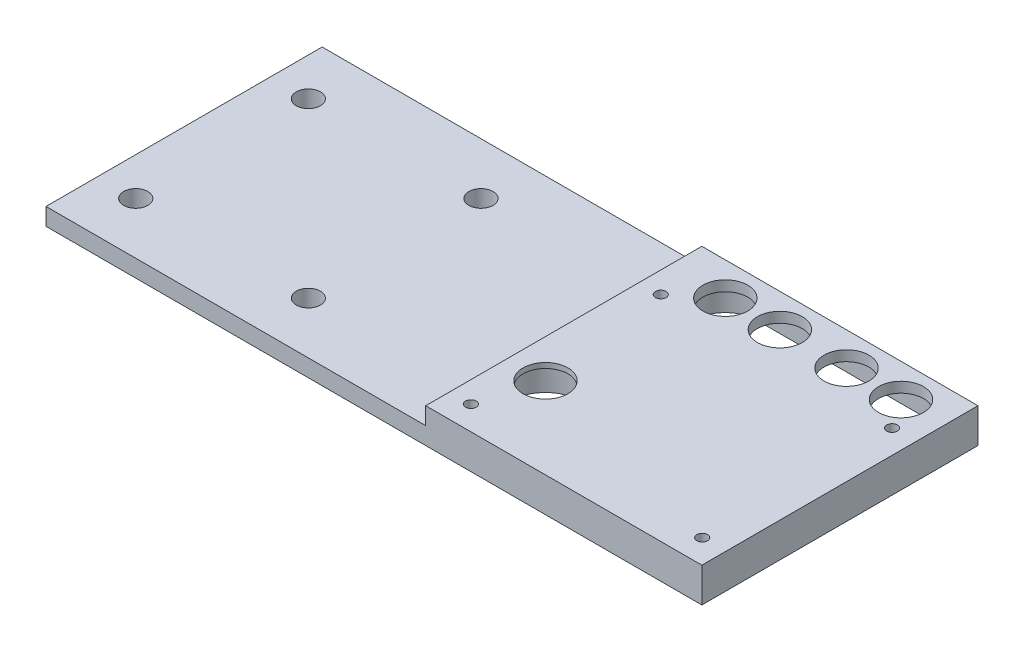
SolidWorks part; units mm, degrees
ref_plane "Front Plane" through (0, 0, 0) normal (0, 0, 1) x (1, 0, 0)
ref_plane "Top Plane" through (0, 0, 0) normal (0, 1, 0) x (1, 0, 0)
ref_plane "Right Plane" through (0, 0, 0) normal (1, 0, 0) x (0, 0, -1)
sketch "Sketch1" plane through (0, 0, 0) normal (0, 1, 0) x (1, 0, 0)
  line L1 (-95, 40) -> (95, 40)
  line L2 (-95, 40) -> (-95, -40)
  line L3 (-95, -40) -> (95, -40)
  line L4 (95, 40) -> (95, -40)
  line L5 (-95, 40) -> (95, -40) construction
  line L6 (-95, -40) -> (95, 40) construction
  point P0 (0, 0)
  dimension "D1" = 80
  dimension "D2" = 190
extrude "Boss-Extrude1" add sketch "Sketch1" along normal blind 5
sketch "Sketch3" plane through (0, 5, 0) normal (0, 1, 0) x (1, 0, 0)
  line L0 (-95, -40) -> (95, -40) construction
  line L1 (95, 40) -> (15, 40)
  line L2 (95, 40) -> (95, -40)
  line L3 (95, -40) -> (15, -40)
  line L4 (15, 40) -> (15, -40)
extrude "Boss-Extrude2" add sketch "Sketch3" along normal blind 5
sketch "Sketch5" plane through (0, 0, 0) normal (0, -1, 0) x (1, 0, 0)
  line L0 (31.4, -30.4) -> (82.3, -30.4) construction
  line L1 (95, 40) -> (95, -40) construction
  line L2 (95, -40) -> (-95, -40) construction
  circle A0 centre (31.4, -30.4) radius 6.5
  circle A1 centre (47.2, -30.4) radius 6.5
  circle A2 centre (66.5, -30.4) radius 6.5
  circle A3 centre (82.3, -30.4) radius 6.5
  dimension "D1" = 13
  dimension "D2" = 15.8
  dimension "D3" = 15.8
  dimension "D4" = 19.3
  dimension "D5" = 12.7
  dimension "D6" = 9.6
extrude "Cut-Extrude2" cut sketch "Sketch5" against normal through all
sketch "Sketch6" plane through (0, 0, 0) normal (0, -1, 0) x (1, 0, 0)
  line L0 (31.4, -21.4) -> (82.3, -21.4)
  line L1 (82.3, -39.4) -> (31.4, -39.4)
  arc A0 (82.3, -21.4) -> (82.3, -39.4) centre (82.3, -30.4) cw
  arc A1 (31.4, -39.4) -> (31.4, -21.4) centre (31.4, -30.4) cw
  circle A2 centre (31.4, -30.4) radius 6.5 construction
  circle A3 centre (82.3, -30.4) radius 6.5 construction
  dimension "D1" = 9
extrude "Cut-Extrude3" cut sketch "Sketch6" against normal offset from surface (7 mm away) 3 up to face at (31.4, 10, -36.9)
sketch "Sketch7" plane through (0, 0, 0) normal (0, -1, 0) x (1, 0, 0)
  line L0 (-84, 0) -> (-95, 0) construction
  line L1 (-84, 25) -> (-34, 25) construction
  line L2 (-84, 25) -> (-84, -25) construction
  line L3 (-84, -25) -> (-34, -25) construction
  line L4 (-34, 25) -> (-34, -25) construction
  line L5 (-95, -40) -> (-95, 40) construction
  circle A0 centre (-84, 25) radius 3.5
  circle A1 centre (-34, 25) radius 3.5
  circle A2 centre (-84, -25) radius 3.5
  circle A3 centre (-34, -25) radius 3.5
  dimension "D1" = 7
  dimension "D2" = 50
  dimension "D3" = 11
extrude "Cut-Extrude4" cut sketch "Sketch7" against normal through all
sketch "Sketch8" plane through (0, 0, 0) normal (0, -1, 0) x (1, 0, 0)
  circle A0 centre (26.1, 16.4) radius 6.5
  circle A2 centre (31.4, -30.4) radius 6.5 construction
  point P2 (23.1936, 12.9709)
  point P4 (36.7, 10.0028)
  dimension "D1" = 5.3
  dimension "D2" = 46.8
  dimension "D3" = 13
extrude "Cut-Extrude5" cut sketch "Sketch8" against normal through all
sketch "Sketch4" plane through (0, 10, 0) normal (0, 1, 0) x (1, 0, 0)
  line L1 (21.15, 21.95) -> (88.15, 21.95) construction
  line L2 (21.15, 21.95) -> (21.15, -33.05) construction
  line L3 (21.15, -33.05) -> (88.15, -33.05) construction
  line L4 (88.15, 21.95) -> (88.15, -33.05) construction
  circle A0 centre (21.15, 21.95) radius 1.55
  circle A1 centre (88.15, 21.95) radius 1.55
  circle A2 centre (21.15, -33.05) radius 1.55
  circle A3 centre (88.15, -33.05) radius 1.55
  circle A4 centre (31.4, 30.4) radius 6.5 construction
  dimension "D1" = 3.1
  dimension "D4" = 8.45
  dimension "D5" = 10.25
  dimension "D2" = 55
  dimension "D3" = 67
extrude "Cut-Extrude1" cut sketch "Sketch4" against normal through all
sketch "Sketch9" plane through (0, 0, 0) normal (0, -1, 0) x (1, 0, 0)
  circle A0 centre (21.15, -21.95) radius 3.5
  circle A1 centre (88.15, -21.95) radius 3.5
  circle A2 centre (21.15, 33.05) radius 3.5
  circle A3 centre (88.15, 33.05) radius 3.5
  dimension "D1" = 7
extrude "Cut-Extrude6" cut sketch "Sketch9" against normal offset from surface (7 mm away) 3 up to face at (88.15, 10, -20.4)
sketch "Sketch10" plane through (0, 0, 0) normal (0, -1, 0) x (1, 0, 0)
  circle A0 centre (26.1, 16.4) radius 10
  dimension "D1" = 20
extrude "Cut-Extrude7" cut sketch "Sketch10" against normal offset from surface (8.5 mm away) 1.5 up to face at (88.15, 10, -20.4)
